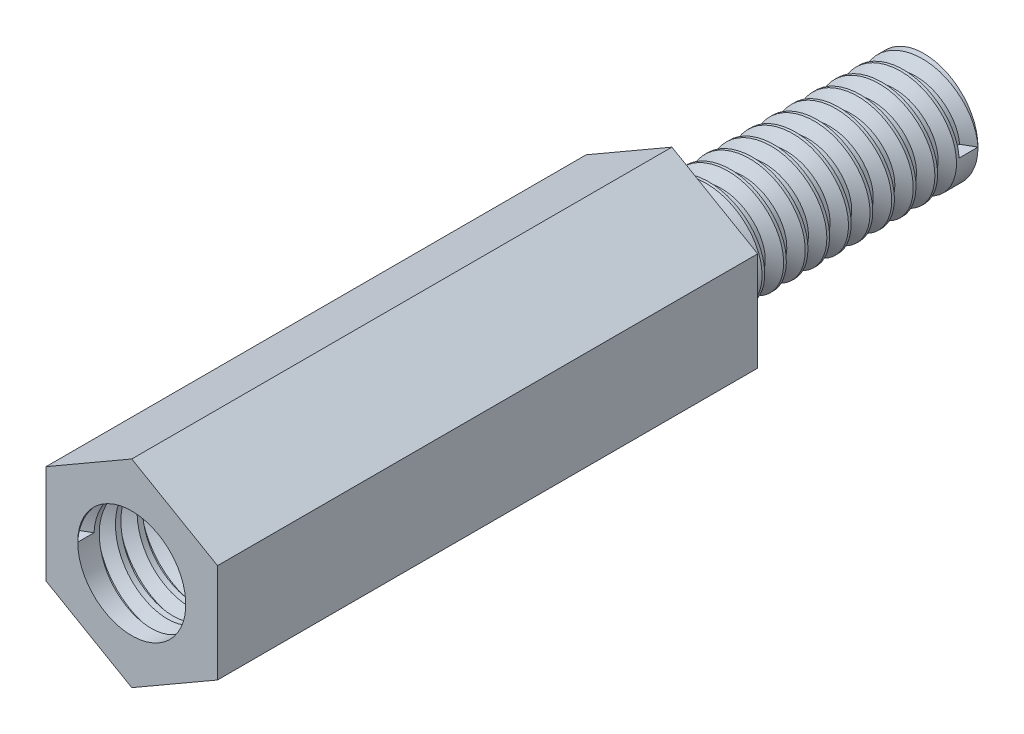
SolidWorks part; units mm, degrees
ref_plane "Front Plane" through (0, 0, 0) normal (0, 0, 1) x (1, 0, 0)
ref_plane "Top Plane" through (0, 0, 0) normal (0, 1, 0) x (1, 0, 0)
ref_plane "Right Plane" through (0, 0, 0) normal (1, 0, 0) x (0, 0, -1)
sketch "Sketch1" plane through (0, 0, 0) normal (0, 0, 1) x (1, 0, 0)
  line L1 (-2.3816, -1.375) -> (0, -2.75)
  line L2 (0, -2.75) -> (2.3816, -1.375)
  line L3 (2.3816, -1.375) -> (2.3816, 1.375)
  line L4 (2.3816, 1.375) -> (0, 2.75)
  line L5 (0, 2.75) -> (-2.3816, 1.375)
  line L6 (-2.3816, 1.375) -> (-2.3816, -1.375)
  circle A0 centre (0, 0) radius 2.3816 construction
  dimension "D1" = 5.5
extrude "Boss-Extrude1" add sketch "Sketch1" along normal blind 15
sketch "Sketch2" plane through (0, 0, 15) normal (0, 0, 1) x (1, 0, 0)
  circle A0 centre (0, 0) radius 1.5
  dimension "D1" = 3
extrude "Cut-Extrude1" cut sketch "Sketch2" against normal blind 7
sketch "Sketch3" plane through (0, 0, 0) normal (0, 0, -1) x (-1, 0, 0)
  circle A0 centre (0, 0) radius 1.5
  dimension "D1" = 3
extrude "Boss-Extrude2" add sketch "Sketch3" along normal blind 7
thread "Thread1" pitch 0.6 method cut profile "Thread Profile1" start angle 0, offset 0, length 0, pitch 0.6, diameter 3
ref_plane "Plane1" through (1.5, 0, -7) normal (0, -1, 0) x (1, 0, 0)
sketch "Thread Profile1" plane through (1.5, 0, -7) normal (0, -1, 0) x (1, 0, 0)
  line L0 (0, 0) -> (0, 0.6) construction
  line L11 (0, 0) -> (0, 0.525)
  line L12 (0, 0.525) -> (-0.3248, 0.3375)
  line L13 (-0.3248, 0.3375) -> (-0.3248, 0.1875)
  line L15 (-0.3248, 0.1875) -> (0, 0)
  line L17 (-0.3248, 0.2625) -> (0, 0.2625) construction
  point P2 (0, 0)
  dimension "Pitch" = 0.6
  dimension "Profile_Angle" = 60
  dimension "Profile_Land" = 0.15
  dimension "Profile_Height" = 0.3248
thread "Thread2" pitch 0.6 method cut profile "Thread Profile2" start angle 0, offset 0, length 0, pitch 0.6, diameter 3
ref_plane "Plane2" through (-1.5, 0, 15) normal (0, -1, 0) x (-1, 0, 0)
sketch "Thread Profile2" plane through (-1.5, 0, 15) normal (0, -1, 0) x (-1, 0, 0)
  line L0 (0, 0) -> (0, 0.6) construction
  line L1 (0, 0) -> (0.3248, 0.1875)
  line L2 (0.3248, 0.1875) -> (0.3248, 0.2625)
  line L3 (0.3248, 0.2625) -> (0, 0.45)
  line L4 (0.3248, 0.225) -> (0, 0.225) construction
  line L11 (0, 0) -> (0, 0.45)
  point P2 (0, 0)
  dimension "Pitch" = 0.6
  dimension "Profile_Angle" = 60
  dimension "Profile_Land" = 0.075
  dimension "Profile_Height" = 0.3248
